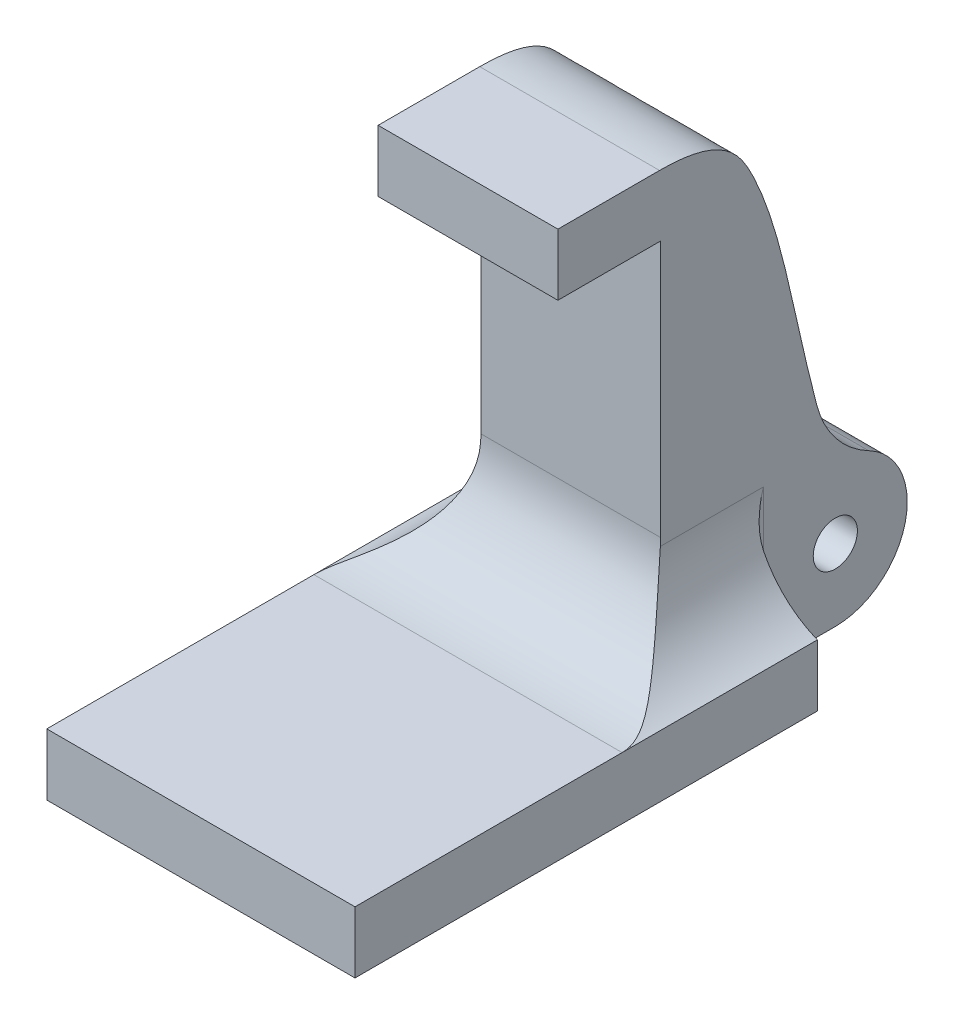
SolidWorks part; units mm, degrees
ref_plane "Front Plane" through (0, 0, 0) normal (0, 0, 1) x (1, 0, 0)
ref_plane "Top Plane" through (0, 0, 0) normal (0, 1, 0) x (1, 0, 0)
ref_plane "Right Plane" through (0, 0, 0) normal (1, 0, 0) x (0, 0, -1)
sketch "Sketch1" plane through (0, 0, 0) normal (0, 1, 0) x (1, 0, 0)
  line L0 (0, -64.9732) -> (0, 0) construction
  line L1 (-8.75, 0) -> (8.75, 0)
  line L2 (8.75, 0) -> (8.75, -15)
  line L3 (8.75, -15) -> (15, -15)
  line L4 (15, -15) -> (15, -60)
  line L5 (15, -60) -> (-15, -60)
  line L6 (-15, -15) -> (-15, -60)
  line L7 (-8.75, -15) -> (-15, -15)
  line L8 (-8.75, 0) -> (-8.75, -15)
  point P13 (0, -60)
  dimension "D1" = 30
  dimension "D2" = 45
  dimension "D3" = 15
  dimension "D4" = 17.5
extrude "Boss-Extrude1" add sketch "Sketch1" along normal blind 6
sketch "Sketch3" plane through (-8.75, 0, 0) normal (-1, 0, 0) x (0, 0, 1)
  line L10 (14, 6) -> (14, 7)
  line L11 (0, 7) -> (0, 6)
  line L12 (0, 0) -> (15, 0) construction
  line L13 (14, 6) -> (0, 6)
  line L14 (0, 6) -> (15, 6) construction
  arc A0 (14, 7) -> (0, 7) centre (7, 7) ccw
  dimension "D2" = 7
  dimension "D1" = 7
extrude "Boss-Extrude2" add sketch "Sketch3" against normal up to surface (17.5 mm away) up to face at (8.75, 3, 7.5)
sketch "Sketch5" plane through (-8.75, 0, 0) normal (-1, 0, 0) x (0, 0, 1)
  line L0 (7, 14) -> (7, 0) construction
  line L1 (0, 0) -> (15, 0) construction
  arc A0 (14, 7) -> (0, 7) centre (7, 7) ccw construction
  circle A1 centre (7, 7) radius 2.15
  dimension "D1" = 4.3
  dimension "D2" = 7
extrude "Cut-Extrude1" cut sketch "Sketch5" against normal up to surface (17.5 mm away) up to face at (8.75, 5.5, 9.6667)
fillet "Fillet1" radius 7 1 edges at (0, 0, 0)
sketch "Sketch6" plane through (0, 6, 0) normal (0, 1, 0) x (1, 0, 0)
  line L0 (0, -60) -> (0, 0) construction
  line L1 (-15, -60) -> (15, -60) construction
  line L2 (8.75, 0) -> (-8.75, 0) construction
  line L3 (2.25, -15) -> (-2.25, -15)
  line L4 (2.25, -15) -> (2.25, 0)
  line L5 (2.25, 0) -> (-2.25, 0)
  line L6 (-2.25, -15) -> (-2.25, 0)
  line L7 (2.25, -15) -> (-2.25, 0) construction
  line L8 (2.25, 0) -> (-2.25, -15) construction
  line L10 (8.75, -15) -> (-8.75, -15) construction
  point P5 (0, -7.5)
  dimension "D1" = 4.5
extrude "Cut-Extrude3" cut sketch "Sketch6" along normal blind 8 and the other way blind 8
sketch "Sketch7" plane through (8.75, 0, 0) normal (1, 0, 0) x (0, 0, -1)
  line L0 (-24, 6) -> (-24, 41)
  line L1 (-60, 6) -> (-15, 6) construction
  line L2 (-24, 41) -> (-34, 41)
  line L3 (-34, 41) -> (-34, 47)
  line L4 (-34, 47) -> (-24.1105, 47)
  line L6 (-14, 6) -> (-14, 7)
  line L8 (-24, 6) -> (-14, 6)
  line L10 (-19.2414, 47) -> (-2.1273, 47) construction
  arc A0 (-14, 7) -> (-7.1795, 13.9977) centre (-7, 7) cw
  circle A3 centre (-7, 7) radius 2.15 construction
  circle A4 centre (-7, 7) radius 2.15 construction
  arc A6 (0, 7) -> (-14, 7) centre (-7, 7) ccw construction
  spline S0 degree 3 poles (-24.1105, 47) (-17.8893, 47) (-11.6942, 37.8193) (-10.867, 25.4552) (-7.1795, 13.9977) knots 0 0 0 0 0.265029 1 1 1 1
  dimension "D5" = 0
  dimension "D1" = 10
  dimension "D2" = 35
  dimension "D3" = 6
  dimension "D4" = 10
extrude "Boss-Extrude3" add sketch "Sketch7" against normal up to surface (17.5 mm away) up to face at (-8.75, 7, 9.15)
sketch "Sketch8" plane through (-2.25, 0, 0) normal (1, 0, 0) x (0, 0, -1)
  line L3 (-15, 6) -> (-15, 7)
  line L5 (-7, 15) -> (-7, 7)
  line L6 (-15, 6) -> (-7, 6)
  line L7 (-7, 6) -> (-7, 7)
  arc A0 (-15, 7) -> (-7, 15) centre (-7, 7) cw
extrude "Cut-Extrude4" cut sketch "Sketch8" along normal up to surface (4.5 mm away) up to face at (2.25, 5.9213, 10.0967)
fillet "Fillet3" radius 10 3 edges at (0, 6, 24) (8.75, 6, 19.5) (-8.75, 6, 19.5)
fillet "Fillet6" radius 1 2 edges at (8.75, 7.6351, 15) (-8.75, 7.6351, 15)
fillet "Fillet7" radius 10 1 edges at (5.5, 13.9977, 7.1795)
